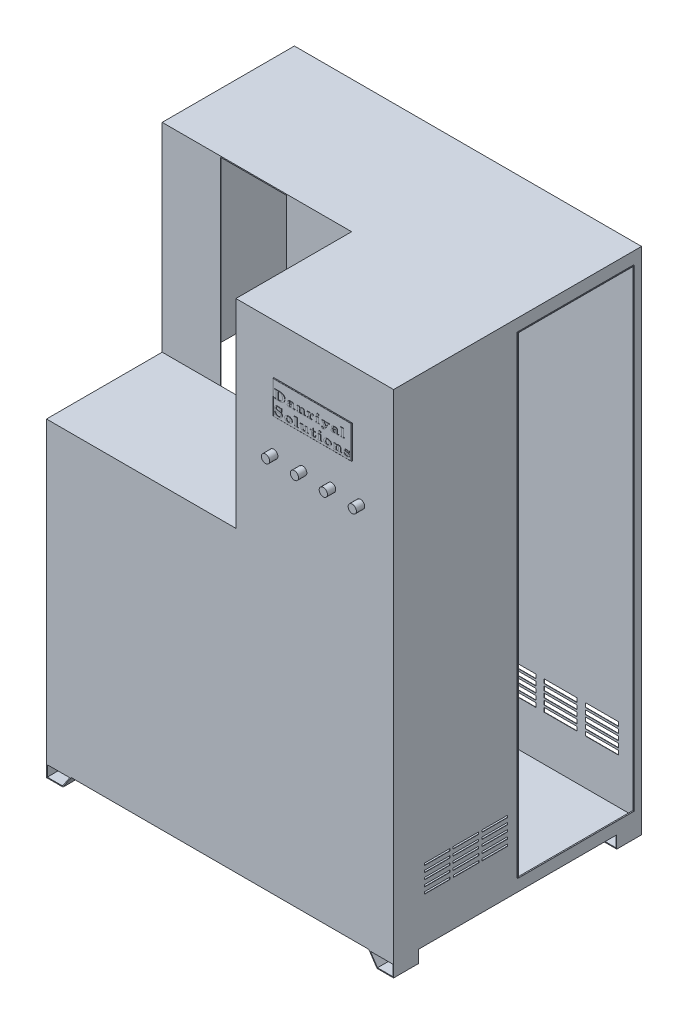
SolidWorks part; units mm, degrees
ref_plane "Front Plane" through (0, 0, 0) normal (0, 0, 1) x (1, 0, 0)
ref_plane "Top Plane" through (0, 0, 0) normal (0, 1, 0) x (1, 0, 0)
ref_plane "Right Plane" through (0, 0, 0) normal (1, 0, 0) x (0, 0, -1)
sketch "Sketch1" plane through (0, 0, 0) normal (0, 1, 0) x (1, 0, 0)
  line L1 (533.4, 381) -> (-533.4, 381)
  line L2 (533.4, 381) -> (533.4, -381)
  line L3 (533.4, -381) -> (-533.4, -381)
  line L4 (-533.4, 381) -> (-533.4, -381)
  line L5 (533.4, 381) -> (-533.4, -381) construction
  line L6 (533.4, -381) -> (-533.4, 381) construction
  point P0 (0, 0)
  dimension "D1" = 762
  dimension "D2" = 1066.8
extrude "Boss-Extrude1" add sketch "Sketch1" along normal blind 1 contours L1 L4 L3 L2
sketch "Sketch2" plane through (0, 1, 0) normal (0, 1, 0) x (1, 0, 0)
  line L0 (533.4, 381) -> (533.4, -381) construction
  line L1 (533.4, -381) -> (-533.4, -381) construction
  line L2 (-533.4, 381) -> (-533.4, -381) construction
  line L3 (533.4, 381) -> (-533.4, 381) construction
  line L4 (533.4, 381) -> (533.4, -381)
  line L5 (533.4, -381) -> (-533.4, -381)
  line L6 (-533.4, 381) -> (-533.4, -381)
  line L7 (533.4, 381) -> (-533.4, 381)
  line L8 (-532.4, 380) -> (-532.4, -380)
  line L9 (532.4, -380) -> (-532.4, -380)
  line L10 (532.4, 380) -> (532.4, -380)
  line L11 (532.4, 380) -> (-532.4, 380)
  line M9 (533.4, -381) -> (533.4, 381)
  line M10 (533.4, 381) -> (-533.4, 381)
  line M11 (-533.4, 381) -> (-533.4, -381)
  line M12 (-533.4, -381) -> (533.4, -381)
  dimension "D1" = 1
extrude "Boss-Extrude2" add sketch "Sketch2" along normal blind 914.4 contours L11 L10 L9 L8 M12 M9 M10 M11
sketch "Sketch4" plane through (0, 915.4, 0) normal (0, 1, 0) x (1, 0, 0)
  line L0 (533.4, 381) -> (-533.4, 381) construction
  line L1 (533.4, 381) -> (-533.4, 381)
  line L2 (532.4, 380) -> (-532.4, 380) construction
  line L3 (532.4, 380) -> (-532.4, 380)
  line L4 (-533.4, 381) -> (-533.4, -25.4)
  line L5 (-533.4, 381) -> (-533.4, -381) construction
  line L6 (-532.4, 380) -> (-532.4, -25.4)
  line L7 (-532.4, 380) -> (-532.4, -380) construction
  line L8 (-532.4, -25.4) -> (-533.4, -25.4)
  line L9 (533.4, 381) -> (533.4, -25.4)
  line L10 (533.4, -381) -> (533.4, 381) construction
  line L11 (532.4, 380) -> (532.4, -25.4)
  line L12 (533.4, -25.4) -> (532.4, -25.4)
  dimension "D1" = 406.4
  dimension "D2" = 406.4
extrude "Boss-Extrude4" add sketch "Sketch4" along normal blind 609.6
sketch "Sketch5" plane through (0, 1525, 0) normal (0, 1, 0) x (1, 0, 0)
  line L1 (533.4, -25.4) -> (533.4, 381) construction
  line L2 (533.4, 381) -> (-533.4, 381) construction
  line L3 (-533.4, 381) -> (-533.4, -25.4) construction
  line L4 (533.4, -25.4) -> (533.4, 381)
  line L5 (533.4, 381) -> (-533.4, 381)
  line L6 (-533.4, 381) -> (-533.4, -25.4)
  line L7 (533.4, -25.4) -> (-533.4, -25.4)
extrude "Boss-Extrude5" add sketch "Sketch5" along normal blind 3.175
sketch "Sketch6" plane through (532.4, 0, 0) normal (-1, 0, 0) x (0, 0, 1)
  line L1 (25.4, 1528.175) -> (24.4, 1528.175)
  line L2 (25.4, 1528.175) -> (25.4, 915.4)
  line L3 (25.4, 915.4) -> (24.4, 915.4)
  line L4 (24.4, 1528.175) -> (24.4, 915.4)
  dimension "D1" = 1
extrude "Boss-Extrude6" add sketch "Sketch6" along normal blind 683.26
sketch "Sketch7" plane through (0, 0, 25.4) normal (0, 0, 1) x (1, 0, 0)
  line L0 (-533.4, 915.4) -> (533.4, 915.4) construction
  line L1 (-532.4, 1525) -> (-354.06, 1525)
  line L2 (-532.4, 1525) -> (-532.4, 915.4)
  line L3 (-532.4, 915.4) -> (-354.06, 915.4)
  line L4 (-354.06, 1525) -> (-354.06, 915.4)
  dimension "D1" = 203.2
extrude "Boss-Extrude7" add sketch "Sketch7" against normal blind 1
sketch "Sketch8" plane through (0, 915.4, 0) normal (0, 1, 0) x (1, 0, 0)
  line L0 (-533.4, -25.4) -> (-533.4, -381)
  line L3 (533.4, -25.4) -> (-533.4, -25.4)
  line L4 (533.4, 381) -> (533.4, -381) construction
  line L5 (533.4, 381) -> (533.4, -381)
  line L6 (-533.4, -381) -> (533.4, -381) construction
  line L7 (-533.4, -381) -> (533.4, -381)
  line M5 (533.4, -25.4) -> (532.4, -25.4)
  line M6 (532.4, -25.4) -> (532.4, -380)
  line M7 (532.4, -380) -> (-532.4, -380)
  line M8 (-532.4, -380) -> (-532.4, -25.4)
  line M9 (-532.4, -25.4) -> (-533.4, -25.4)
  line M10 (-533.4, -25.4) -> (-533.4, -381)
  line M11 (-533.4, -381) -> (533.4, -381)
  line M12 (533.4, -381) -> (533.4, -25.4)
extrude "Boss-Extrude8" add sketch "Sketch8" along normal blind 1 contours M12 M5 M6 M7 M8 M9 M10 M11 | L3 M6 M8 M7
sketch "Sketch10" plane through (0, 0, 381) normal (0, 0, 1) x (1, 0, 0)
  line L0 (0, 0) -> (0, -91.2356) construction
  line L1 (533.4, 0) -> (533.4, -38.1)
  line L2 (533.4, -38.1) -> (482.6, -38.1)
  line L3 (482.6, -38.1) -> (457.2, 0)
  line L4 (533.4, 0) -> (-533.4, 0) construction
  line L5 (457.2, 0) -> (533.4, 0)
  line L6 (461.946, -2.54) -> (530.86, -2.54)
  line L7 (530.86, -2.54) -> (530.86, -35.56)
  line L8 (530.86, -35.56) -> (483.9594, -35.56)
  line L9 (483.9594, -35.56) -> (461.946, -2.54)
  line L10 (-483.9594, -35.56) -> (-461.946, -2.54)
  line L11 (-530.86, -35.56) -> (-483.9594, -35.56)
  line L12 (-530.86, -2.54) -> (-530.86, -35.56)
  line L13 (-461.946, -2.54) -> (-530.86, -2.54)
  line L14 (-457.2, 0) -> (-533.4, 0)
  line L15 (-482.6, -38.1) -> (-457.2, 0)
  line L16 (-533.4, -38.1) -> (-482.6, -38.1)
  line L17 (-533.4, 0) -> (-533.4, -38.1)
  dimension "D1" = 38.1
  dimension "D2" = 76.2
  dimension "D3" = 50.8
  dimension "D4" = 2.54
extrude "Boss-Extrude9" add sketch "Sketch10" against normal blind 76.2
mirror "Mirror1" about plane through (0, 0, 0) normal (0, 0, 1) of "Boss-Extrude9"
sketch "Sketch11" plane through (533.4, 0, 0) normal (1, 0, 0) x (0, 0, -1)
  line L0 (-25.4, 916.4) -> (-25.4, 1) construction
  line L1 (380, 1) -> (-380, 1) construction
  line L2 (-25.4, 1528.175) -> (381, 1528.175) construction
  line L3 (0, 1490.075) -> (355.6, 1490.075)
  line L4 (0, 1490.075) -> (0, 39.1)
  line L5 (0, 39.1) -> (355.6, 39.1)
  line L6 (355.6, 1490.075) -> (355.6, 39.1)
  line L7 (381, 1528.175) -> (381, -38.1) construction
  line L8 (-25.4, 1528.175) -> (-25.4, 916.4) construction
  line L9 (-1, 1491.075) -> (356.6, 1491.075)
  line L10 (356.6, 1491.075) -> (356.6, 38.1)
  line L11 (-1, 38.1) -> (356.6, 38.1)
  line L12 (-1, 1491.075) -> (-1, 38.1)
  line L13 (-381, 439.15) -> (-25.4, 439.15) construction
  line L14 (-381, 916.4) -> (-381, -38.1) construction
  line L15 (-381, 439.15) -> (-380, 1) construction
  line L16 (-380, 1) -> (-25.4, 1) construction
  line L17 (-380.5, 220.075) -> (-25.4, 220.075) construction
  line L18 (-202.95, 220.075) -> (-202.7, 1) construction
  line L19 (-202.95, 220.075) -> (-25.4, 1) construction
  line L20 (-25.4, 220.075) -> (-202.7, 1) construction
  line L21 (-202.7, 1) -> (-380.5, 220.075) construction
  line L22 (-202.95, 220.075) -> (-380, 1) construction
  line L23 (-114.175, 110.5375) -> (-114.175, 220.075) construction
  line L24 (-291.6, 110.5375) -> (-291.6, 220.075) construction
  line L25 (-291.6, 110.5375) -> (-114.175, 110.5375) construction
  line L26 (-25.4, 110.5375) -> (-114.175, 110.5375) construction
  line L27 (-291.6, 220.075) -> (-202.825, 110.5375) construction
  line L28 (-202.825, 110.5375) -> (-114.175, 220.075) construction
  line L29 (-114.175, 220.075) -> (-25.4, 110.5375) construction
  line L31 (-285.9243, 220.075) -> (-208.1129, 220.075)
  line L32 (-285.9243, 220.075) -> (-285.9243, 213.6866)
  line L33 (-285.9243, 213.6866) -> (-208.1129, 213.6866)
  line L34 (-208.1129, 220.075) -> (-208.1129, 213.6866)
  line L35 (-197.7725, 220.075) -> (-119.3452, 220.075)
  line L36 (-197.7725, 220.075) -> (-197.7725, 213.6866)
  line L37 (-197.7725, 213.6866) -> (-119.3452, 213.6866)
  line L38 (-119.3452, 220.075) -> (-119.3452, 213.6866)
  line L39 (-30.5702, 220.075) -> (-108.9975, 220.075)
  line L40 (-30.5702, 220.075) -> (-30.5702, 213.6866)
  line L41 (-30.5702, 213.6866) -> (-108.9975, 213.6866)
  line L42 (-108.9975, 220.075) -> (-108.9975, 213.6866)
  dimension "D1" = 38.1
  dimension "D2" = 25.4
  dimension "D3" = 25.4
  dimension "D4" = 38.1
  dimension "D6" = 77.8114
  dimension "D7" = 95.0757
  dimension "D5" = 1
extrude "Cut-Extrude5" cut sketch "Sketch11" against normal blind 1 contours L34 L31 L32 L33 | L38 L35 L36 L37 | L39 L42 L41 L40
pattern_linear "LPattern1" count 5 spacing 19.05 along (0, -1, -0.0023) of "Cut-Extrude5"
sketch "Sketch12" plane through (533.4, 0, 0) normal (1, 0, 0) x (0, 0, -1)
  line L0 (0, 1490.075) -> (355.6, 1490.075) construction
  line L1 (-1, 1491.075) -> (356.6, 1491.075) construction
  line L2 (356.6, 1491.075) -> (356.6, 38.1) construction
  line L3 (355.6, 1490.075) -> (355.6, 39.1) construction
  line L4 (-1, 1491.075) -> (-1, 38.1) construction
  line L5 (0, 1490.075) -> (0, 39.1) construction
  line L6 (-1, 38.1) -> (356.6, 38.1) construction
  line L7 (0, 39.1) -> (355.6, 39.1) construction
  line L8 (0, 1490.075) -> (355.6, 1490.075)
  line L9 (-1, 1491.075) -> (356.6, 1491.075)
  line L10 (-304.8, 0) -> (304.8, 0)
  line L11 (304.8, 0) -> (304.8, -38.1)
  line L12 (304.8, -38.1) -> (381, -38.1)
  line L13 (381, -38.1) -> (381, 1528.175)
  line L14 (381, 1528.175) -> (-25.4, 1528.175)
  line L15 (-25.4, 1528.175) -> (-25.4, 916.4)
  line L16 (-25.4, 916.4) -> (-381, 916.4)
  line L17 (-381, 916.4) -> (-381, -38.1)
  line L18 (-381, -38.1) -> (-304.8, -38.1)
  line L19 (-304.8, -38.1) -> (-304.8, 0)
  line L20 (-304.8, 0) -> (304.8, 0)
  line L21 (304.8, 0) -> (304.8, -38.1)
  line L22 (304.8, -38.1) -> (381, -38.1)
  line L23 (381, -38.1) -> (381, 1528.175)
  line L24 (381, 1528.175) -> (-25.4, 1528.175)
  line L25 (-25.4, 1528.175) -> (-25.4, 916.4)
  line L26 (-25.4, 916.4) -> (-381, 916.4)
  line L27 (-381, 916.4) -> (-381, -38.1)
  line L28 (-381, -38.1) -> (-304.8, -38.1)
  line L29 (-304.8, -38.1) -> (-304.8, 0)
  line L30 (356.6, 1491.075) -> (356.6, 38.1)
  line L31 (355.6, 1490.075) -> (355.6, 39.1)
  line L32 (-1, 1491.075) -> (-1, 38.1)
  line L33 (0, 1490.075) -> (0, 39.1)
  line L34 (-1, 38.1) -> (356.6, 38.1)
  line L35 (0, 39.1) -> (355.6, 39.1)
  dimension "D1" = 0
sketch "Sketch14" plane through (533.4, 0, 0) normal (1, 0, 0) x (0, 0, -1)
  line L0 (-1, 38.1) -> (356.6, 38.1) construction
  line L1 (0, 39.1) -> (355.6, 39.1) construction
  line L2 (355.6, 1490.075) -> (355.6, 39.1) construction
  line L3 (356.6, 1491.075) -> (356.6, 38.1) construction
  line L4 (0, 1490.075) -> (0, 39.1) construction
  line L5 (0, 1490.075) -> (355.6, 1490.075) construction
  line L6 (-1, 1491.075) -> (-1, 38.1) construction
  line L7 (-1, 1491.075) -> (356.6, 1491.075) construction
  line L8 (-1, 38.1) -> (356.6, 38.1)
  line L9 (0, 39.1) -> (355.6, 39.1)
  line L10 (355.6, 1490.075) -> (355.6, 39.1)
  line L11 (356.6, 1491.075) -> (356.6, 38.1)
  line L12 (0, 1490.075) -> (0, 39.1)
  line L13 (0, 1490.075) -> (355.6, 1490.075)
  line L14 (-1, 1491.075) -> (-1, 38.1)
  line L15 (-1, 1491.075) -> (356.6, 1491.075)
extrude "Boss-Extrude10" add sketch "Sketch14" along normal blind 2.54
sketch "Sketch15" plane through (533.4, 0, 0) normal (1, 0, 0) x (0, 0, -1)
  line L0 (0, 39.1) -> (355.6, 39.1) construction
  line L1 (355.6, 1490.075) -> (355.6, 39.1) construction
  line L2 (0, 1490.075) -> (0, 39.1) construction
  line L3 (0, 1490.075) -> (355.6, 1490.075) construction
  line L4 (0, 39.1) -> (355.6, 39.1)
  line L5 (355.6, 1490.075) -> (355.6, 39.1)
  line L6 (0, 1490.075) -> (0, 39.1)
  line L7 (0, 1490.075) -> (355.6, 1490.075)
extrude "Cut-Extrude7" cut sketch "Sketch15" against normal blind 2.54
sketch "Sketch16" plane through (0, 0, 381) normal (0, 0, 1) x (1, 0, 0)
  line L0 (-533.4, 1528.175) -> (533.4, 1528.175) construction
  line L1 (406.4, 1375.775) -> (165.1, 1375.775)
  line L2 (406.4, 1375.775) -> (406.4, 1274.175)
  line L3 (406.4, 1274.175) -> (165.1, 1274.175)
  line L4 (165.1, 1375.775) -> (165.1, 1274.175)
  line L5 (406.4, 1375.775) -> (165.1, 1274.175) construction
  line L6 (406.4, 1274.175) -> (165.1, 1375.775) construction
  line L7 (533.4, 1491.075) -> (533.4, 38.1) construction
  point P0 (285.75, 1324.975)
  dimension "D1" = 152.4
  dimension "D2" = 127
  dimension "D3" = 368.3
  dimension "D4" = 254
sketch "Sketch18" plane through (-533.4, 0, 0) normal (-1, 0, 0) x (0, 0, 1)
  line L0 (25.4, 916.4) -> (381, 916.4) construction
  line L1 (-317.5, 852.9) -> (317.5, 852.9)
  line L2 (-317.5, 852.9) -> (-317.5, 63.5)
  line L3 (-317.5, 63.5) -> (317.5, 63.5)
  line L4 (317.5, 852.9) -> (317.5, 63.5)
  line L5 (381, 916.4) -> (381, -38.1) construction
  line L6 (-381, 1528.175) -> (-381, -38.1) construction
  line L7 (-304.8, 0) -> (304.8, 0) construction
  dimension "D1" = 63.5
  dimension "D2" = 63.5
  dimension "D3" = 63.5
  dimension "D4" = 63.5
extrude "Cut-Extrude8" cut sketch "Sketch18" against normal blind 25.4
sketch "Sketch19" plane through (0, 0, -381) normal (0, 0, -1) x (-1, 0, 0)
  line L0 (0, 0) -> (0, 228.6) construction
  line L1 (0, 228.6) -> (-533.4, 228.6) construction
  line L2 (-533.4, 1528.175) -> (-533.4, -38.1) construction
  line L3 (-336.55, 228.6) -> (-234.95, 228.6)
  line L4 (-463.55, 228.6) -> (-361.95, 228.6)
  line L5 (-463.55, 228.6) -> (-463.55, 215.9)
  line L6 (-463.55, 215.9) -> (-361.95, 215.9)
  line L7 (-361.95, 228.6) -> (-361.95, 215.9)
  line L8 (-336.55, 215.9) -> (-234.95, 215.9)
  line L9 (-234.95, 228.6) -> (-234.95, 215.9)
  line L10 (-336.55, 228.6) -> (-336.55, 215.9)
  line L11 (-209.55, 228.6) -> (-107.95, 228.6)
  line L12 (-209.55, 215.9) -> (-107.95, 215.9)
  line L13 (-107.95, 228.6) -> (-107.95, 215.9)
  line L14 (-209.55, 228.6) -> (-209.55, 215.9)
  dimension "D1" = 228.6
  dimension "D2" = 12.7
  dimension "D3" = 101.6
  dimension "D4" = 69.85
  dimension "D6" = 25.4
  dimension "D5" = 3
extrude "Cut-Extrude9" cut sketch "Sketch19" against normal blind 6.35
pattern_linear "LPattern2" count 5 spacing 19.05 along (0, -1, 0) of "Cut-Extrude9"
sketch "Sketch20" plane through (0, 0, 25.4) normal (0, 0, 1) x (1, 0, 0)
  line L0 (-532.4, 1525) -> (532.4, 1525) construction
  line L1 (49.8, 1525) -> (532.4, 1525)
  line L2 (49.8, 1525) -> (49.8, 916.4)
  line L3 (49.8, 916.4) -> (532.4, 916.4)
  line L4 (532.4, 1525) -> (532.4, 916.4)
  line L5 (-533.4, 916.4) -> (533.4, 916.4) construction
  line L6 (533.4, 1491.075) -> (533.4, 38.1) construction
  dimension "D1" = 1
  dimension "D2" = 482.6
extrude "Cut-Extrude10" cut sketch "Sketch20" against normal blind 6.35 contours L2 L3 L4 L1
sketch "Sketch21" plane through (0, 0, 25.4) normal (0, 0, 1) x (1, 0, 0)
  line L0 (-532.4, 1525) -> (532.4, 1525) construction
  line L1 (533.4, 1528.175) -> (49.8, 1528.175)
  line L2 (533.4, 1528.175) -> (533.4, 1525)
  line L3 (533.4, 1525) -> (49.8, 1525)
  line L4 (49.8, 1528.175) -> (49.8, 1525)
  dimension "D1" = 483.6
extrude "Boss-Extrude13" add sketch "Sketch21" along normal blind 355.6
sketch "Sketch22" plane through (0, 0, 25.4) normal (0, 0, 1) x (1, 0, 0)
  line L0 (532.4, 1525) -> (533.4, 1525) construction
  line L1 (533.4, 916.4) -> (532.4, 916.4) construction
  line L2 (532.4, 1525) -> (532.4, 916.4) construction
  line L3 (533.4, 1525) -> (533.4, 916.4) construction
  line L4 (532.4, 1525) -> (533.4, 1525)
  line L5 (533.4, 916.4) -> (532.4, 916.4)
  line L6 (532.4, 1525) -> (532.4, 916.4)
  line L7 (533.4, 1525) -> (533.4, 916.4)
extrude "Boss-Extrude14" add sketch "Sketch22" along normal up to surface (355.6 mm away) up to face at (291.6, 1526.5875, 381)
sketch "Sketch24" plane through (0, 916.4, 0) normal (0, 1, 0) x (1, 0, 0)
  line L2 (49.8, -25.4) -> (49.8, -381)
  line L5 (48.8, -25.4) -> (48.8, -381)
  line L6 (48.8, -381) -> (49.8, -381)
  line L7 (49.8, -25.4) -> (48.8, -25.4)
  line L8 (-533.4, -381) -> (532.4, -381) construction
  dimension "D1" = 1
extrude "Boss-Extrude18" add sketch "Sketch24" along normal up to surface (611.775 mm away) contours L5 L6 L2 L7 up to face at (16.6, 1528.175, 8.4667)
sketch "Sketch25" plane through (0, 916.4, 0) normal (0, 1, 0) x (1, 0, 0)
  line L4 (49.8, -24.4) -> (49.8, -381)
  line L18 (49.8, -24.4) -> (49.8, -381)
  line L22 (49.8, -381) -> (532.4, -381)
  line L24 (49.8, -381) -> (532.4, -381)
  line L26 (532.4, -381) -> (532.4, -24.4)
  line L27 (532.4, -381) -> (532.4, -24.4)
  line L28 (532.4, -24.4) -> (49.8, -24.4)
  line L29 (532.4, -24.4) -> (49.8, -24.4)
  dimension "D1" = 0
extrude "Cut-Extrude11" cut sketch "Sketch25" against normal blind 1
sketch "Sketch26" plane through (0, 0, 381) normal (0, 0, 1) x (1, 0, 0)
  line L0 (49.8, 1525) -> (532.4, 1525) construction
  line L1 (532.4, 915.4) -> (532.4, 1525) construction
  line L2 (49.8, 1525) -> (49.8, 915.4) construction
  line L3 (49.8, 915.4) -> (532.4, 915.4) construction
  line L4 (49.8, 1525) -> (532.4, 1525)
  line L5 (532.4, 915.4) -> (532.4, 1525)
  line L6 (49.8, 1525) -> (49.8, 915.4)
  line L7 (49.8, 915.4) -> (532.4, 915.4)
extrude "Boss-Extrude19" add sketch "Sketch26" against normal blind 1
extrude "Boss-Extrude20" add sketch "Sketch16" along normal blind 2.54 contours L1 L4 L3 L2
fillet "Fillet2" radius 1.27 4 edges at (165.1, 1324.975, 383.54) (285.75, 1274.175, 383.54) (406.4, 1324.975, 383.54) (285.75, 1375.775, 383.54)
sketch "Sketch27" plane through (0, 0, 381) normal (0, 0, 1) x (1, 0, 0)
  line L0 (406.4, 1274.175) -> (165.1, 1274.175) construction
  line L1 (48.8, 1528.175) -> (48.8, 916.4) construction
  circle A0 centre (165.1, 1172.575) radius 12.7
  circle A1 centre (254, 1172.575) radius 12.7
  circle A2 centre (342.9, 1172.575) radius 12.7
  circle A3 centre (431.8, 1172.575) radius 12.7
  dimension "D1" = 25.4
  dimension "D5" = 88.9
  dimension "D2" = 101.6
  dimension "D3" = 116.3
  dimension "D4" = 4
extrude "Boss-Extrude21" add sketch "Sketch27" along normal blind 25.4
sketch "Sketch28" plane through (0, 0, 383.54) normal (0, 0, 1) x (1, 0, 0)
  line L0 (166.37, 1324.975) -> (405.13, 1324.975) construction
  line L1 (166.37, 1374.505) -> (166.37, 1275.445) construction
  line L2 (405.13, 1275.445) -> (405.13, 1374.505) construction
  text T0 "Danriyal \r\nSolutions" font "Century Schoolbook" height in points 100
extrude "Boss-Extrude22" add sketch "Sketch28" along normal blind 1
equation "\"in\"=0.03937"
